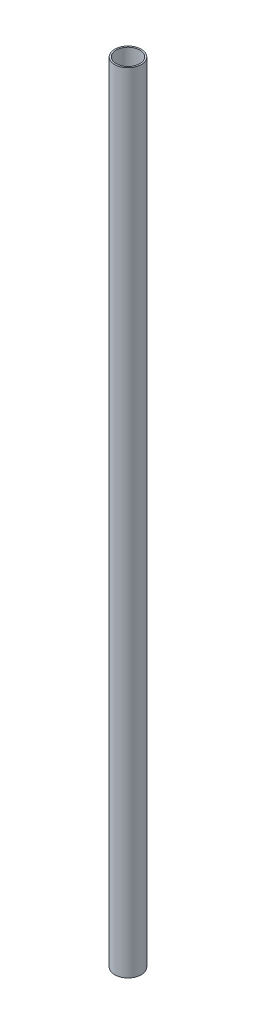
SolidWorks part; units mm, degrees
ref_plane "Front Plane" through (0, 0, 0) normal (0, 0, 1) x (1, 0, 0)
ref_plane "Top Plane" through (0, 0, 0) normal (0, 1, 0) x (1, 0, 0)
ref_plane "Right Plane" through (0, 0, 0) normal (1, 0, 0) x (0, 0, -1)
sketch "Sketch1" plane through (0, 0, 0) normal (0, 1, 0) x (1, 0, 0)
  circle A0 centre (0, 0) radius 6.096
  circle A1 centre (0, 0) radius 6.858
extrude "Boss-Extrude1" add sketch "Sketch1" along normal blind 406.4
